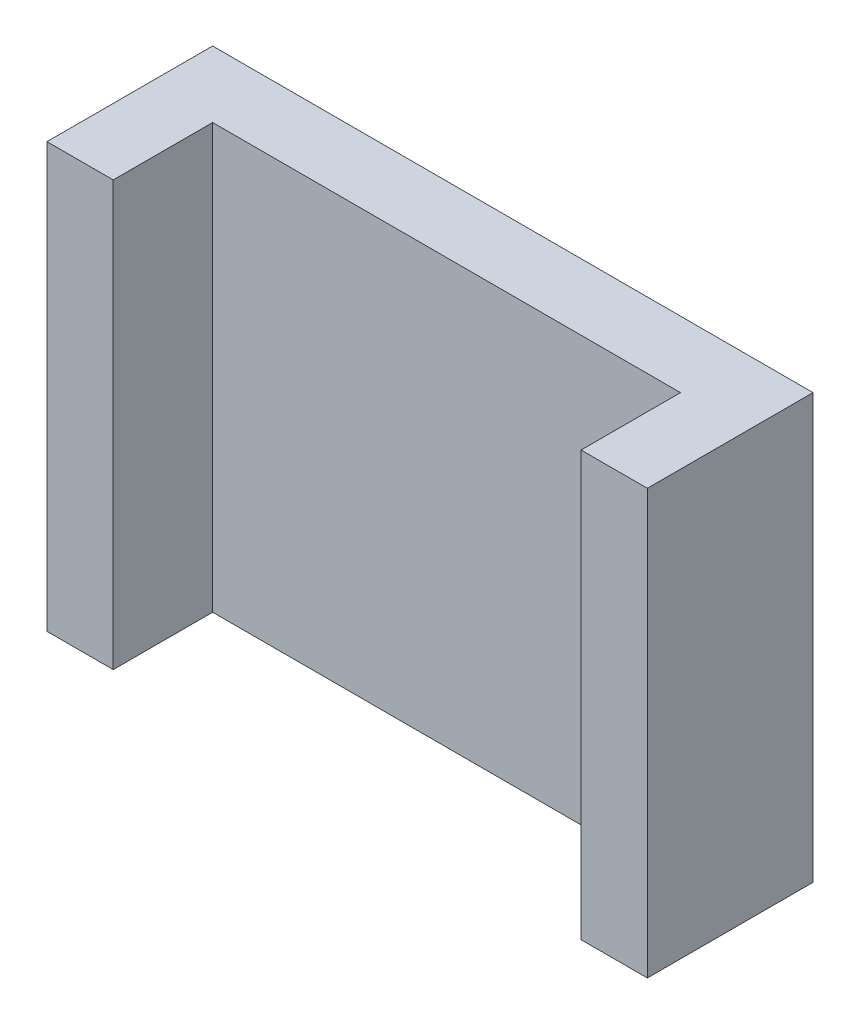
SolidWorks part; units mm, degrees
ref_plane "Front Plane" through (0, 0, 0) normal (0, 0, 1) x (1, 0, 0)
ref_plane "Top Plane" through (0, 0, 0) normal (0, 1, 0) x (1, 0, 0)
ref_plane "Right Plane" through (0, 0, 0) normal (1, 0, 0) x (0, 0, -1)
sketch "Sketch1" plane through (0, 0, 0) normal (0, 0, 1) x (1, 0, 0)
  line L1 (0, 0) -> (45.3, 0)
  line L2 (0, 0) -> (0, 32)
  line L3 (0, 32) -> (45.3, 32)
  line L4 (45.3, 0) -> (45.3, 32)
extrude "Boss-Extrude1" add sketch "Sketch1" along normal blind 5 contours L3 L4 L1 L2
sketch "Sketch2" plane through (0, 0, 5) normal (0, 0, 1) x (1, 0, 0)
  line L0 (0, 0) -> (45.3, 0) construction
  line L1 (0, 32) -> (5, 32)
  line L2 (0, 32) -> (0, 0)
  line L3 (0, 0) -> (5, 0)
  line L4 (5, 32) -> (5, 0)
  line L10 (45.3, 32) -> (40.3, 32)
  line L11 (45.3, 32) -> (45.3, 0)
  line L12 (45.3, 0) -> (40.3, 0)
  line L13 (40.3, 32) -> (40.3, 0)
  line M9 (0, 32) -> (0, 0)
  line M10 (0, 0) -> (45.3, 0)
  line M12 (45.3, 32) -> (0, 32)
extrude "Boss-Extrude2" add sketch "Sketch2" along normal blind 7.5 contours L4 M12 M9 M10 | L10 L13 L12 L11 region at (2.5, 16, 5)
